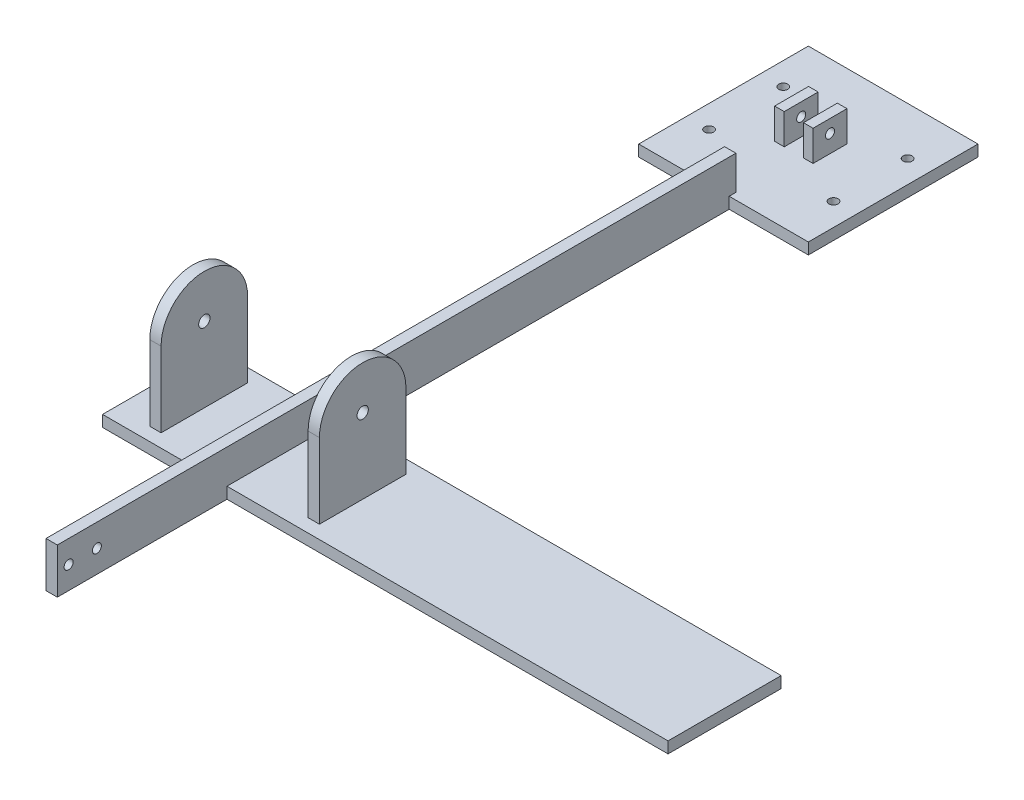
SolidWorks part; units mm, degrees
ref_plane "Front Plane" through (0, 0, 0) normal (0, 0, 1) x (1, 0, 0)
ref_plane "Top Plane" through (0, 0, 0) normal (0, 1, 0) x (1, 0, 0)
ref_plane "Right Plane" through (0, 0, 0) normal (1, 0, 0) x (0, 0, -1)
sketch "Sketch2" plane through (0, 0, 0) normal (0, 1, 0) x (1, 0, 0)
  line L0 (-75, 150) -> (-75, 0) construction
  line L5 (0, 0) -> (-150, 0)
  line L6 (0, 0) -> (0, 150)
  line L7 (0, 150) -> (-150, 150)
  line L8 (-150, 0) -> (-150, 150)
  line L9 (-150, 75) -> (0, 75) construction
  circle A0 centre (-130, 42.2411) radius 4
  circle A1 centre (-20, 42.2411) radius 4
  circle A2 centre (-20, 107.7589) radius 4
  circle A3 centre (-130, 107.7589) radius 4
  dimension "D3" = 8
  dimension "D4" = 8
  dimension "D1" = 150
  dimension "D2" = 150
  dimension "D5" = 20
  dimension "D6" = 20
extrude "Boss-Extrude2" add sketch "Sketch2" along normal blind 10
sketch "Sketch3" plane through (0, 0, 0) normal (0, 1, 0) x (1, 0, 0)
  line L0 (-150, 150) -> (-150, 0) construction
  line L1 (-80, 5.9547) -> (-70, 5.9547)
  line L2 (-80, 5.9547) -> (-80, -594.0453)
  line L3 (-80, -594.0453) -> (-70, -594.0453)
  line L4 (-70, 5.9547) -> (-70, -594.0453)
  dimension "D1" = 10
  dimension "D2" = 70
  dimension "D3" = 600
extrude "Boss-Extrude3" add sketch "Sketch3" along normal blind 40
sketch "Sketch4" plane through (0, 0, 0) normal (0, 1, 0) x (1, 0, 0)
  line L1 (-180, -344.0453) -> (320, -344.0453)
  line L2 (-180, -344.0453) -> (-180, -444.0453)
  line L3 (-180, -444.0453) -> (320, -444.0453)
  line L4 (320, -344.0453) -> (320, -444.0453)
  line L5 (-80, -594.0453) -> (-70, -594.0453) construction
  line L6 (-80, 5.9547) -> (-80, -594.0453) construction
  dimension "D1" = 100
  dimension "D2" = 150
  dimension "D3" = 500
  dimension "D4" = 100
extrude "Boss-Extrude4" add sketch "Sketch4" along normal blind 10
sketch "Sketch5" plane through (0, 0, 0) normal (1, 0, 0) x (0, 0, -1)
  line L0 (-432.2853, 10) -> (-432.2853, 76.3488)
  line L1 (-444.0453, 10) -> (-344.0453, 10) construction
  line L2 (-394.0453, 10) -> (-394.0453, 219.1776) construction
  line L3 (-444.0453, 10) -> (-344.0453, 10) construction
  line L4 (-355.8053, 10) -> (-355.8053, 76.3488)
  line L5 (-432.2853, 10) -> (-355.8053, 10)
  arc A0 (-432.2853, 76.3488) -> (-394.0453, 114.5888) centre (-394.0453, 76.3488) cw
  arc A1 (-355.8053, 76.3488) -> (-394.0453, 114.5888) centre (-394.0453, 76.3488) ccw
  circle A2 centre (-394.0453, 76.3488) radius 5
  dimension "D2" = 10
  dimension "D1" = 38.24
extrude "Boss-Extrude5" add sketch "Sketch5" against normal blind 10
ref_plane "Plane1" through (-75, 0, 0) normal (1, 0, 0) x (0, 0, -1)
mirror "Mirror1" about plane through (-75, 0, 0) normal (1, 0, 0) of "Boss-Extrude5"
ref_plane "Plane2" through (-58, 0, 0) normal (1, 0, 0) x (0, 0, -1)
sketch "Sketch7" plane through (-58, 0, 0) normal (1, 0, 0) x (0, 0, -1)
  line L0 (0, 10) -> (150, 10) construction
  line L1 (77.165, 10) -> (77.165, 69.6913) construction
  line L2 (62.165, 10) -> (92.165, 10)
  line L3 (62.165, 10) -> (62.165, 37)
  line L4 (62.165, 37) -> (92.165, 37)
  line L5 (92.165, 10) -> (92.165, 37)
  circle A0 centre (77.165, 25.5245) radius 4
  point P10 (0, 0)
  point P11 (76.8964, 25.557)
  point P12 (76.9641, 25.5245)
  point P13 (92.165, 32)
  dimension "D2" = 8
  dimension "D1" = 27
  dimension "15" = 15
extrude "Boss-Extrude6" add sketch "Sketch7" against normal blind 8.5
mirror "Mirror2" about plane through (-75, 0, 0) normal (1, 0, 0) of "Boss-Extrude6"
sketch "Sketch8" plane through (-70, 0, 0) normal (1, 0, 0) x (0, 0, -1)
  line L0 (-594.0453, 40) -> (-594.0453, 0) construction
  circle A0 centre (-584.0453, 20) radius 4
  circle A1 centre (-559.0453, 20) radius 4
  dimension "D1" = 8
  dimension "D2" = 8
  dimension "D3" = 10
  dimension "D4" = 25
extrude "Cut-Extrude1" cut sketch "Sketch8" against normal through all
